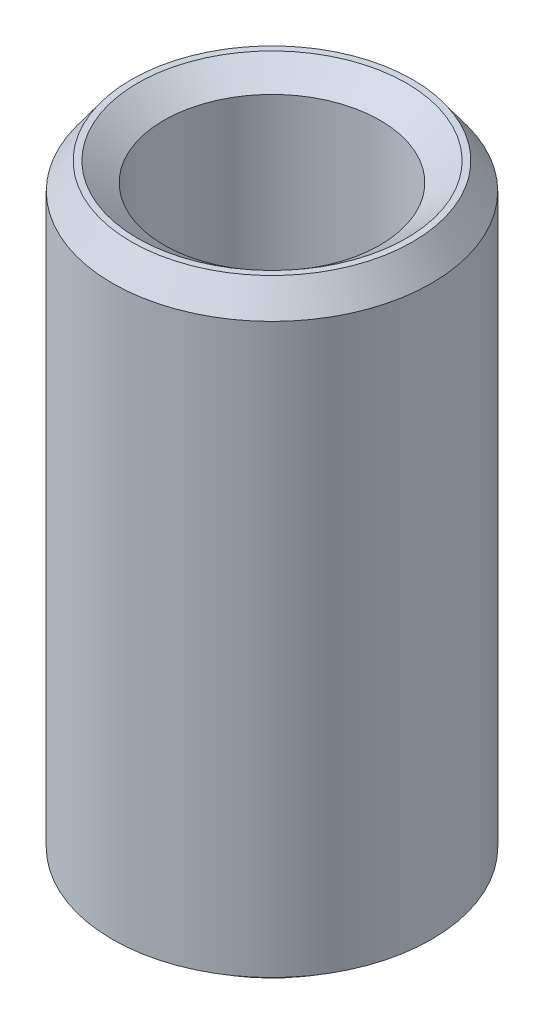
SolidWorks part; units mm, degrees
ref_plane "Front Plane" through (0, 0, 0) normal (0, 0, 1) x (1, 0, 0)
ref_plane "Top Plane" through (0, 0, 0) normal (0, 1, 0) x (1, 0, 0)
ref_plane "Right Plane" through (0, 0, 0) normal (1, 0, 0) x (0, 0, -1)
sketch "Sketch1" plane through (0, 0, 0) normal (0, 1, 0) x (1, 0, 0)
  circle A0 centre (0, 0) radius 12.5
  dimension "SLEEVE_OD" = 25
extrude "Boss-Extrude1" add sketch "Sketch1" along normal blind 48.0464
sketch "Sketch2" plane through (0, 0, 0) normal (0, 1, 0) x (1, 0, 0)
  circle A0 centre (0, 0) radius 8.4654
  dimension "BORE_D" = 16.9307
extrude "Cut-Extrude1" cut sketch "Sketch2" along normal through all
chamfer "Chamfer1" distance 2.0618 angle 35.82 4 edges at (0, 48.0464, 8.4654) (0, 0, 8.4654) (0, 0, 12.5) (0, 48.0464, 12.5) first distance on face at (0, 48.0464, 8.4654) first distance on face at (0, 0, 8.4654) first distance on face at (0, 48.0464, 12.5)
